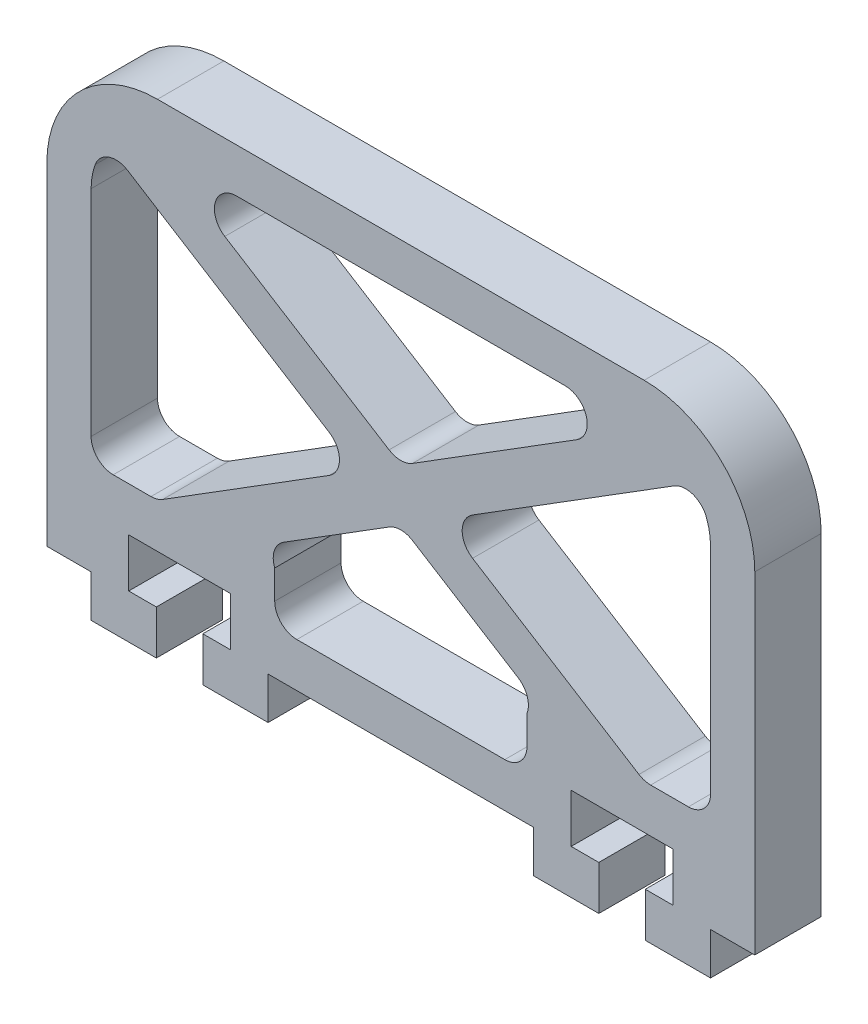
SolidWorks part; units mm, degrees
ref_plane "Front Plane" through (0, 0, 0) normal (0, 0, 1) x (1, 0, 0)
ref_plane "Top Plane" through (0, 0, 0) normal (0, 1, 0) x (1, 0, 0)
ref_plane "Right Plane" through (0, 0, 0) normal (1, 0, 0) x (0, 0, -1)
sketch "Sketch1" plane through (0, 0, 0) normal (0, 0, 1) x (1, 0, 0)
  line L0 (-10, -11.9) -> (-10, 10) construction
  line L1 (-16, 10) -> (16, 10)
  line L2 (-16, 10) -> (-16, -10)
  line L3 (-16, -10) -> (16, -10)
  line L4 (16, 10) -> (16, -10)
  line L5 (-16, 10) -> (16, -10) construction
  line L6 (-16, -10) -> (16, 10) construction
  line L7 (-16, -10) -> (-6, -10)
  line L9 (-14, -11.9) -> (-6, -11.9)
  line L10 (-6, -10) -> (-6, -11.9)
  line L11 (0, 10) -> (0, -10) construction
  line L12 (-11.05, -9.9) -> (-8.95, -9.9)
  line L13 (-11.05, -9.9) -> (-11.05, -11.9)
  line L14 (-11.05, -11.9) -> (-8.95, -11.9)
  line L15 (-8.95, -9.9) -> (-8.95, -11.9)
  line L16 (-11.05, -9.9) -> (-8.95, -11.9) construction
  line L17 (-11.05, -11.9) -> (-8.95, -9.9) construction
  line L18 (-12.3, -7.7) -> (-7.7, -7.7)
  line L19 (-12.3, -7.7) -> (-12.3, -9.9)
  line L20 (-12.3, -9.9) -> (-7.7, -9.9)
  line L21 (-7.7, -7.7) -> (-7.7, -9.9)
  line L22 (-12.3, -7.7) -> (-7.7, -9.9) construction
  line L23 (-12.3, -9.9) -> (-7.7, -7.7) construction
  line L24 (12.3, -7.7) -> (7.7, -7.7)
  line L25 (12.3, -7.7) -> (12.3, -9.9)
  line L26 (12.3, -9.9) -> (7.7, -9.9)
  line L27 (7.7, -7.7) -> (7.7, -9.9)
  line L28 (11.05, -9.9) -> (8.95, -9.9)
  line L29 (11.05, -9.9) -> (11.05, -11.9)
  line L30 (11.05, -11.9) -> (8.95, -11.9)
  line L31 (8.95, -9.9) -> (8.95, -11.9)
  line L32 (16, -10) -> (6, -10)
  line L33 (6, -10) -> (6, -11.9)
  line L34 (14, -11.9) -> (6, -11.9)
  line L36 (-14, -11.9) -> (-14, -10)
  line L37 (14, -11.9) -> (14, -10)
  point P0 (0, 0)
  point P11 (-10, -10.9)
  point P16 (-10, -8.8)
  dimension "D1" = 32
  dimension "D2" = 20
  dimension "D3" = 1.9
  dimension "D4" = 8
  dimension "D5" = 2.1
  dimension "D6" = 2
  dimension "D7" = 2.2
  dimension "D8" = 4.6
  dimension "D9" = 2
extrude "Boss-Extrude2" add sketch "Sketch1" along normal blind 3 contours L31 L26 L27 L24 L25 L29 L3 L4 L1 L2 L13 L20 L19 L18 L21 L15 | L3 L15 L9 L10 | L13 L3 L9 | L34 L31 L3 L33 | L3 L29 L34 region at (0, 0.2943, 0) region at (-12.525, -10.95, 0) region at (12.525, -10.95, 0) region at (-7.475, -10.95, 0) region at (7.475, -10.95, 0)
fillet "Fillet1" radius 5 2 edges at (16, 10, 1.5) (-16, 10, 1.5)
sketch "Sketch2" plane through (0, 0, 3) normal (0, 0, 1) x (1, 0, 0)
  line L0 (-6, -10) -> (6, -10) construction
  line L1 (16, -10) -> (-16, -10)
  line L2 (16, -10) -> (16, 10)
  line L3 (16, 10) -> (-16, 10)
  line L4 (-16, -10) -> (-16, 10)
  line L5 (16, -10) -> (-16, 10) construction
  line L6 (16, 10) -> (-16, -10) construction
  line L8 (16.53, -9.152) -> (-15.47, 10.848)
  line L9 (15.47, 10.848) -> (-16.53, -9.152)
  line L10 (15.47, -10.848) -> (-16.53, 9.152)
  line L11 (16.53, 9.152) -> (-15.47, -10.848)
  line L36 (-16, 5) -> (-16, -10) construction
  line L60 (11, 8) -> (-11, 8)
  line L61 (14, -5.7) -> (14, 5)
  line L62 (-14, -5.7) -> (-5.7, -5.7)
  line L63 (-5.7, -5.7) -> (-5.7, -8)
  line L64 (-5.7, -8) -> (5.7, -8)
  line L65 (5.7, -8) -> (5.7, -5.7)
  line L66 (5.7, -5.7) -> (14, -5.7)
  line L67 (14, -5.7) -> (14, 5)
  line L68 (11, 8) -> (-11, 8)
  line L70 (-14, -5.7) -> (-5.7, -5.7)
  line L71 (-5.7, -5.7) -> (-5.7, -8)
  line L72 (-5.7, -8) -> (5.7, -8)
  line L73 (5.7, -8) -> (5.7, -5.7)
  line L74 (5.7, -5.7) -> (14, -5.7)
  line L80 (-14, 5) -> (-14, -5.7)
  line L81 (-14, 5) -> (-14, -5.7)
  arc A4 (14, 5) -> (11, 8) centre (11, 5) ccw
  arc A5 (14, 5) -> (11, 8) centre (11, 5) ccw
  arc A8 (-11, 8) -> (-14, 5) centre (-11, 5) ccw
  arc A9 (-11, 8) -> (-14, 5) centre (-11, 5) ccw
  point P0 (0, 0)
  dimension "D1" = 1
  dimension "D2" = 1
  dimension "D3" = 2
extrude "Cut-Extrude1" cut sketch "Sketch2" against normal up to next contours L10 L70 L9 | L9 L68 L8 | L11 L8 L74 | L72 L73 L10 L11 L71 region at (0, -5.3754, 3) region at (9.8341, 0.1444, 3) region at (-9.8341, 0.1444, 3) region at (0, 5.7264, 3)
fillet "Fillet2" radius 1 16 edges at (5.7, -8, 1.5) (-5.7, -8, 1.5) (0, -1.1792, 1.5) (11.0068, -5.7, 1.5) (1.8868, 0, 1.5) (10.9132, 8, 1.5) (-10.9132, 8, 1.5) (0, 1.1792, 1.5) (-1.8868, 0, 1.5) (-11.0068, -5.7, 1.5) (14, -5.7, 1.5) (13.1816, 7.0593, 1.5) (-13.1816, 7.0593, 1.5) (-14, -5.7, 1.5) (7.2332, -5.7, 1.5) (-7.2332, -5.7, 1.5)
